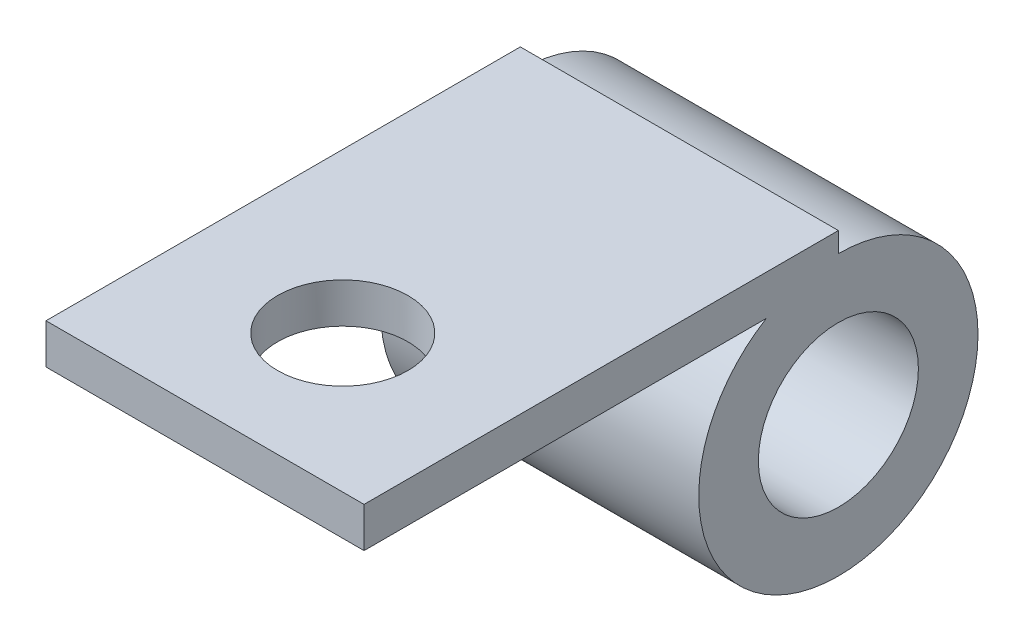
SolidWorks part; units mm, degrees
ref_plane "Front Plane" through (0, 0, 0) normal (0, 0, 1) x (1, 0, 0)
ref_plane "Top Plane" through (0, 0, 0) normal (0, 1, 0) x (1, 0, 0)
ref_plane "Right Plane" through (0, 0, 0) normal (1, 0, 0) x (0, 0, -1)
sketch "Loop Sketch" plane through (0, 0, 0) normal (1, 0, 0) x (0, 0, -1)
  circle A0 centre (0, 0) radius 5.575
extrude "Loop" add sketch "Loop Sketch" along normal mid plane 12.7
ref_axis "Engine Axis" through (6.985, 0, 0) along (-1, 0, 0)
sketch "Tab Sketch" plane through (0, 0, 0) normal (1, 0, 0) x (0, 0, -1)
  line L0 (0, 4.775) -> (-18.94, 4.775)
  line L1 (-18.94, 4.775) -> (-18.94, 6.375)
  line L2 (-18.94, 6.375) -> (0, 6.375)
  line L3 (0, 6.375) -> (0, 4.775)
extrude "Tab" add sketch "Tab Sketch" along normal mid plane 12.7
sketch "Tube Hole Sketch" plane through (0, 0, 0) normal (1, 0, 0) x (0, 0, -1)
  circle A0 centre (0, 0) radius 3.195
extrude "Tube Hole" cut sketch "Tube Hole Sketch" against normal mid plane 14.7
sketch "Mount Hole Sketch" plane through (0, 0, 0) normal (0, 1, 0) x (1, 0, 0)
  circle A0 centre (0, -13.44) radius 2.6
extrude "Mount Hole" cut sketch "Mount Hole Sketch" against normal mid plane 40
